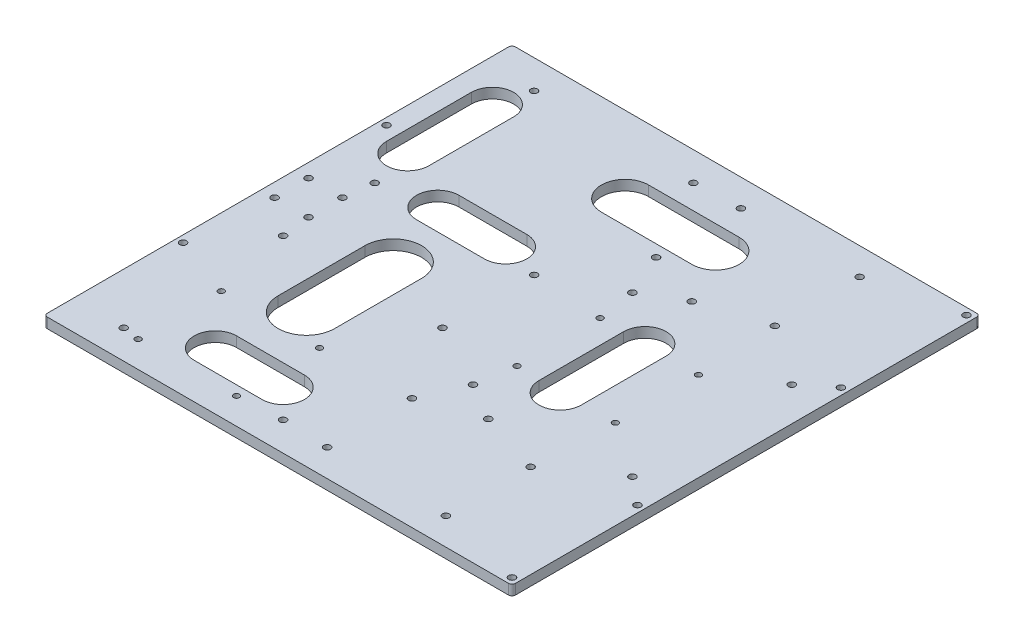
SolidWorks part; units mm, degrees
ref_plane "Спереди" through (0, 0, 0) normal (0, 0, 1) x (1, 0, 0)
ref_plane "Сверху" through (0, 0, 0) normal (0, 1, 0) x (1, 0, 0)
ref_plane "Справа" through (0, 0, 0) normal (1, 0, 0) x (0, 0, -1)
sketch "Эскиз1" plane through (0, 0, 0) normal (0, 1, 0) x (1, 0, 0)
  line L1 (-138, -138) -> (138, -138)
  line L2 (-138, -138) -> (-138, 138)
  line L3 (-138, 138) -> (138, 138)
  line L4 (138, -138) -> (138, 138)
  line L5 (0, 138) -> (0, -138) construction
  line L6 (-138, 0) -> (138, 0) construction
  point P0 (0, 0)
  dimension "D1" = 276
  dimension "D2" = 276
extrude "Бобышка-Вытянуть1" add sketch "Эскиз1" along normal blind 6
fillet "Скругление1" radius 2 4 edges at (138, 3, 138) (-138, 3, 138) (-138, 3, -138) (138, 3, -138)
sketch "Эскиз2" plane through (0, 6, 0) normal (0, 1, 0) x (1, 0, 0)
  line L0 (0, 147.7994) -> (0, 0) construction
  line L1 (0, 0) -> (-164.0684, 0) construction
  line L2 (-164.0684, 0) -> (215.1731, 0) construction
  circle A0 centre (-134, 60) radius 2
  circle A1 centre (134, 60) radius 2
  circle A2 centre (134, -60) radius 2
  circle A3 centre (-134, -60) radius 2
  circle A4 centre (46, 60) radius 2
  circle A5 centre (46, -60) radius 2
  circle A6 centre (134, 134) radius 2
  circle A7 centre (134, -134) radius 2
  dimension "D1" = 134
  dimension "D2" = 60
  dimension "D4" = 134
  dimension "D3" = 46
  dimension "D5" = 134
extrude "Вырез-Вытянуть1" cut sketch "Эскиз2" against normal blind 6
sketch "Эскиз10" plane through (0, 6, 0) normal (0, 1, 0) x (1, 0, 0)
  line L0 (0, 0) -> (99.2175, -171.8497) construction
  line L1 (0, 0) -> (206.3493, 0) construction
  line L2 (13, -97) -> (83, -97) construction
  line L3 (13, 72) -> (83, 72) construction
  line L4 (13, 72) -> (13, 122) construction
  line L5 (13, 122) -> (83, 122) construction
  line L6 (83, 72) -> (83, 122) construction
  line L7 (48, 122) -> (48, 72) construction
  line L8 (13, 97) -> (83, 97) construction
  line L9 (48, -122) -> (48, -72) construction
  line L15 (136, 138) -> (-136, 138) construction
  line L16 (-27.8464, 0) -> (-120, 0) construction
  line L17 (-120, 0) -> (0, 0) construction
  line L19 (-130, -10) -> (-110, -10) construction
  line L20 (-130, -10) -> (-130, 10) construction
  line L21 (-130, 10) -> (-110, 10) construction
  line L22 (-110, -10) -> (-110, 10) construction
  line L23 (-120, 10) -> (-120, -10) construction
  line L24 (-130, 0) -> (-110, 0) construction
  line L25 (0, 0) -> (99.2175, 171.8497) construction
  line L26 (83, -72) -> (83, -122) construction
  line L27 (13, -122) -> (83, -122) construction
  line L28 (13, -72) -> (13, -122) construction
  line L29 (13, -72) -> (83, -72) construction
  line L30 (138, -136) -> (138, 136) construction
  line L32 (138, -138) -> (60, -138) construction
  line L33 (138, -138) -> (138, -103.923) construction
  line L34 (138, -103.923) -> (60, -103.923) construction
  line L35 (60, -138) -> (60, -103.923) construction
  line L36 (83, 122) -> (60, 122) construction
  line L37 (83, 122) -> (83, 103.923) construction
  line L38 (83, 103.923) -> (60, 103.923) construction
  line L39 (60, 122) -> (60, 103.923) construction
  circle A0 centre (13, 122) radius 2
  circle A1 centre (83, 122) radius 2
  circle A2 centre (13, 72) radius 2
  circle A3 centre (83, 72) radius 2
  circle A8 centre (-130, 10) radius 2
  circle A9 centre (-110, 10) radius 2
  circle A10 centre (-110, -10) radius 2
  circle A11 centre (-130, -10) radius 2
  circle A13 centre (0, 0) radius 120 construction
  circle A14 centre (83, -72) radius 2
  circle A15 centre (13, -72) radius 2
  circle A16 centre (83, -122) radius 2
  circle A17 centre (13, -122) radius 2
  point P5 (48, 97)
  point P25 (48, -97)
  dimension "D3" = 4
  dimension "D9" = 23
  dimension "D10" = 18.077
  dimension "D13" = 72
  dimension "D14" = 13
  dimension "D15" = 110
  dimension "D1" = 50
  dimension "D2" = 70
  dimension "D4" = 90
  dimension "D5" = 16
  dimension "D6" = 20
  dimension "D7" = 20
  dimension "D8" = 120
  dimension "D11" = 78
  dimension "D12" = 34.077
extrude "Под стойки и сервы" cut sketch "Эскиз10" against normal blind 7
sketch "Эскиз3" plane through (0, 6, 0) normal (0, 1, 0) x (1, 0, 0)
  line L0 (0, 147.4317) -> (0, 0) construction
  line L1 (-193.8488, 0) -> (193.8488, 0) construction
  line L2 (138, -136) -> (138, 136) construction
  line L7 (43, 82) -> (43, -82) construction
  line L13 (43, 75) -> (43, -75) construction
  line L14 (-117, -82) -> (33, -82) construction
  line L16 (-117, 82) -> (33, 82) construction
  line L18 (-42, 82) -> (-42, -82) construction
  line L19 (-89.5005, 0) -> (60.4995, 0) construction
  line L20 (-124, -75) -> (40, -75) construction
  line L22 (-124, 75) -> (40, 75) construction
  line L24 (-42, 75) -> (-42, -75) construction
  line L25 (-96.5005, 0) -> (67.4995, 0) construction
  circle A0 centre (-32, 82) radius 2
  circle A1 centre (118, 82) radius 2
  circle A2 centre (125, 75) radius 2
  circle A3 centre (-39, 75) radius 2
  circle A4 centre (118, -82) radius 2
  circle A5 centre (125, -75) radius 2
  circle A6 centre (-32, -82) radius 2
  circle A7 centre (-39, -75) radius 2
  circle A8 centre (-124, 75) radius 2
  circle A10 centre (40, 75) radius 2
  circle A11 centre (33, 82) radius 2
  circle A12 centre (40, -75) radius 2
  circle A13 centre (33, -82) radius 2
  circle A14 centre (-117, -82) radius 2
  circle A15 centre (-124, -75) radius 2
  circle A16 centre (-117, 82) radius 2
  point P3 (43, 0)
  point P8 (43, 0)
  point P22 (-42, 0)
  point P24 (-42, 0)
  dimension "D3" = 95
  dimension "D1" = 150
  dimension "D2" = 164
  dimension "D4" = 150
  dimension "D5" = 164
  dimension "D6" = 180
extrude "150х164" [suppressed] cut sketch "Эскиз3" against normal blind 6
sketch "Эскиз7" plane through (0, 6, 0) normal (0, 1, 0) x (1, 0, 0)
  line L0 (-167.0096, 52) -> (194.2165, 52) construction
  line L2 (-18, 26) -> (98, 26) construction
  line L3 (-18, 26) -> (-18, 78) construction
  line L4 (-18, 78) -> (98, 78) construction
  line L5 (98, 26) -> (98, 78) construction
  line L6 (40, 78) -> (40, 26) construction
  line L7 (-18, 52) -> (98, 52) construction
  line L8 (136, 138) -> (-136, 138) construction
  circle A0 centre (-18, 78) radius 1.75
  circle A1 centre (-18, 26) radius 1.75
  circle A2 centre (98, 78) radius 1.75
  circle A3 centre (98, 26) radius 1.75
  point P2 (40, 52)
  dimension "D3" = 3.5
  dimension "D1" = 116
  dimension "D2" = 52
  dimension "D4" = 40
  dimension "D5" = 60
extrude "Jetson" [suppressed] cut sketch "Эскиз7" against normal blind 6
sketch "Эскиз9" plane through (0, 6, 0) normal (0, 1, 0) x (1, 0, 0)
  line L0 (-18.2911, 15.2367) -> (-18.2911, -61.2367) construction
  line L1 (-18.2911, -61.2367) -> (91.6393, -61.2367) construction
  line L2 (91.6393, -61.2367) -> (91.6393, -138) construction
  line L3 (-136, -138) -> (136, -138) construction
  line L4 (91.6393, -138) -> (129.5083, -138) construction
  line L5 (129.5083, -138) -> (129.5083, 138) construction
  line L6 (136, 138) -> (-136, 138) construction
  line L7 (129.5083, 138) -> (112.5959, 138) construction
  line L8 (112.5959, 138) -> (112.5959, 17.8103) construction
  line L9 (112.5959, 17.8103) -> (-18.2911, 17.8103) construction
  line L10 (-18.2911, 17.8103) -> (-18.2911, 15.2367) construction
  line L11 (-18.2911, -23) -> (230.269, -23) construction
  line L12 (138, -136) -> (138, 136) construction
  line L13 (-7, 2) -> (-7, -48) construction
  line L14 (43, 2) -> (43, -48) construction
  line L15 (43, -48) -> (83, -48) construction
  line L16 (83, -48) -> (83, 2) construction
  line L17 (83, 2) -> (123, 2) construction
  line L18 (123, 2) -> (123, -48) construction
  line L19 (98, -17) -> (128, -17) construction
  line L26 (98, -17) -> (98, 13) construction
  line L27 (98, 13) -> (128, 13) construction
  line L28 (128, -17) -> (128, 13) construction
  line L29 (113, 13) -> (113, -17) construction
  line L30 (98, -2) -> (128, -2) construction
  circle A0 centre (-7, 2) radius 1.8
  circle A1 centre (43, 2) radius 1.8
  circle A2 centre (83, 2) radius 1.8
  circle A3 centre (123, 2) radius 1.8
  circle A4 centre (123, -48) radius 1.8
  circle A5 centre (83, -48) radius 1.8
  circle A6 centre (43, -48) radius 1.8
  circle A7 centre (-7, -48) radius 1.8
  circle A8 centre (43, -23) radius 1.8
  circle A9 centre (-7, -23) radius 1.8
  circle A10 centre (83, -23) radius 1.8
  circle A11 centre (123, -23) radius 1.8
  circle A12 centre (123, 62) radius 1.8
  circle A13 centre (123, 122) radius 1.8
  circle A15 centre (123, -108) radius 1.8
  circle A20 centre (98, 13) radius 1.8
  circle A21 centre (128, 13) radius 1.8
  circle A22 centre (98, -17) radius 1.8
  circle A23 centre (128, -17) radius 1.8
  circle A24 centre (98, -29) radius 1.8
  circle A25 centre (128, -29) radius 1.8
  circle A26 centre (128, -59) radius 1.8
  circle A27 centre (98, -59) radius 1.8
  point P61 (113, -2)
  dimension "D1" = 3.6
  dimension "D2" = 50
  dimension "D3" = 40
  dimension "D4" = 40
  dimension "D12" = 30
  dimension "D5" = 25
  dimension "D6" = 60
  dimension "D7" = 60
  dimension "D8" = 115
  dimension "D9" = 15
  dimension "D13" = 30
  dimension "D14" = 10
  dimension "D15" = 140
extrude "Вырез-Вытянуть8" [suppressed] cut sketch "Эскиз9" against normal blind 6
sketch "Эскиз4" plane through (0, 6, 0) normal (0, 1, 0) x (1, 0, 0)
  line L0 (-244.2183, 0) -> (0, 0) construction
  line L1 (0, 0) -> (0, 146.3288) construction
  line L2 (-177.488, 74) -> (64.2486, 74) construction
  line L3 (-138, 136) -> (-138, -136) construction
  line L4 (-108, 27) -> (-14, 27) construction
  line L5 (-108, 27) -> (-108, 121) construction
  line L6 (-108, 121) -> (-14, 121) construction
  line L7 (-14, 27) -> (-14, 121) construction
  line L8 (-61, 121) -> (-61, 27) construction
  line L9 (-108, 74) -> (-14, 74) construction
  line L10 (0, 0) -> (256.1096, 0) construction
  line L11 (24, -47) -> (118, -47) construction
  line L12 (24, -47) -> (24, 47) construction
  line L13 (24, 47) -> (118, 47) construction
  line L14 (118, -47) -> (118, 47) construction
  line L15 (71, 47) -> (71, -47) construction
  line L16 (24, 0) -> (118, 0) construction
  line L17 (138, -136) -> (138, 136) construction
  circle A0 centre (-108, 121) radius 2
  circle A1 centre (-14, 121) radius 2
  circle A2 centre (-14, 27) radius 2
  circle A3 centre (-108, 27) radius 2
  circle A4 centre (-108, -27) radius 2
  circle A5 centre (-14, -27) radius 2
  circle A6 centre (-14, -121) radius 2
  circle A7 centre (-108, -121) radius 2
  circle A8 centre (24, 47) radius 2
  circle A9 centre (118, 47) radius 2
  circle A10 centre (118, -47) radius 2
  circle A11 centre (24, -47) radius 2
  point P6 (-61, 74)
  point P24 (71, 0)
  dimension "D5" = 94
  dimension "D9" = 47
  dimension "D1" = 94
  dimension "D2" = 94
  dimension "D3" = 74
  dimension "D4" = 30
  dimension "D6" = 94
  dimension "D7" = 20
  dimension "D8" = 118
extrude "94х94" cut sketch "Эскиз4" against normal blind 6
sketch "Эскиз8" plane through (0, 6, 0) normal (0, 1, 0) x (1, 0, 0)
  line L1 (27.4655, -24.5) -> (85.4655, -24.5) construction
  line L2 (27.4655, -24.5) -> (27.4655, 24.5) construction
  line L3 (27.4655, 24.5) -> (85.4655, 24.5) construction
  line L4 (85.4655, -24.5) -> (85.4655, 24.5) construction
  line L5 (56.4655, 24.5) -> (56.4655, -24.5) construction
  line L6 (27.4655, 0) -> (85.4655, 0) construction
  line L8 (0, 166.5491) -> (0, 0) construction
  line L9 (0, 0) -> (185.1673, 0) construction
  line L10 (-167.745, -98) -> (174.3629, -98) construction
  line L11 (-98, -122.5) -> (-40, -122.5) construction
  line L12 (-98, -122.5) -> (-98, -73.5) construction
  line L13 (-98, -73.5) -> (-40, -73.5) construction
  line L14 (-40, -122.5) -> (-40, -73.5) construction
  line L15 (-69, -73.5) -> (-69, -122.5) construction
  line L16 (-98, -98) -> (-40, -98) construction
  line L17 (-136, -138) -> (136, -138) construction
  line L18 (-138, 136) -> (-138, -136) construction
  circle A0 centre (85.4655, 24.5) radius 1.75
  circle A1 centre (27.4655, 24.5) radius 1.75
  circle A2 centre (27.4655, -24.5) radius 1.75
  circle A3 centre (85.4655, -24.5) radius 1.75
  circle A4 centre (-40, -73.5) radius 1.75
  circle A5 centre (-98, -73.5) radius 1.75
  circle A6 centre (-98, -122.5) radius 1.75
  circle A7 centre (-40, -122.5) radius 1.75
  point P0 (56.4655, 0)
  point P4 (-69, -98)
  dimension "D5" = 3.5
  dimension "D1" = 58
  dimension "D2" = 49
  dimension "D3" = 40
  dimension "D4" = 40
extrude "RPi4" cut sketch "Эскиз8" against normal blind 6
sketch "Эскиз6" plane through (0, 6, 0) normal (0, 1, 0) x (1, 0, 0)
  line L0 (-70.6279, -104.2964) -> (-30.6279, -104.2964) construction
  line L3 (0, 165.0655) -> (0, 0) construction
  line L4 (0, 0) -> (164.436, 0) construction
  line L5 (-70.6279, -91.7964) -> (-30.6279, -91.7964)
  line L9 (-76.8541, 33.0775) -> (-36.8541, 33.0775) construction
  line L10 (-76.8541, 45.5775) -> (-36.8541, 45.5775)
  line L11 (-76.8541, 20.5775) -> (-36.8541, 20.5775)
  line L13 (-70.6279, -116.7964) -> (-30.6279, -116.7964)
  line L16 (-62.1479, -7.8884) -> (-62.1479, -59.1081) construction
  line L20 (-113.2922, 101.779) -> (-113.2922, 51.779) construction
  line L21 (-125.7922, 101.779) -> (-125.7922, 51.779)
  line L22 (-100.7922, 101.779) -> (-100.7922, 51.779)
  line L23 (-26.2076, 92.8656) -> (27.1824, 92.8656) construction
  line L24 (-26.2076, 106.7739) -> (27.1824, 106.7739)
  line L25 (-26.2076, 78.9573) -> (27.1824, 78.9573)
  line L26 (-78.8638, -7.8884) -> (-78.8638, -59.1081)
  line L29 (-45.4321, -7.8884) -> (-45.4321, -59.1081)
  line L30 (53.8487, 24.5334) -> (53.8487, -25.4666) construction
  line L31 (41.3487, 24.5334) -> (41.3487, -25.4666)
  line L32 (66.3487, 24.5334) -> (66.3487, -25.4666)
  arc A4 (-76.8541, 45.5775) -> (-76.8541, 20.5775) centre (-76.8541, 33.0775) ccw
  arc A5 (-36.8541, 20.5775) -> (-36.8541, 45.5775) centre (-36.8541, 33.0775) ccw
  arc A10 (-125.7922, 101.779) -> (-100.7922, 101.779) centre (-113.2922, 101.779) cw
  arc A11 (-100.7922, 51.779) -> (-125.7922, 51.779) centre (-113.2922, 51.779) cw
  arc A12 (-26.2076, 106.7739) -> (-26.2076, 78.9573) centre (-26.2076, 92.8656) ccw
  arc A13 (27.1824, 78.9573) -> (27.1824, 106.7739) centre (27.1824, 92.8656) ccw
  arc A16 (-70.6279, -91.7964) -> (-70.6279, -116.7964) centre (-70.6279, -104.2964) ccw
  arc A17 (-30.6279, -116.7964) -> (-30.6279, -91.7964) centre (-30.6279, -104.2964) ccw
  arc A18 (-78.8638, -7.8884) -> (-45.4321, -7.8884) centre (-62.1479, -7.8884) cw
  arc A19 (-45.4321, -59.1081) -> (-78.8638, -59.1081) centre (-62.1479, -59.1081) cw
  arc A20 (41.3487, 24.5334) -> (66.3487, 24.5334) centre (53.8487, 24.5334) cw
  arc A21 (66.3487, -25.4666) -> (41.3487, -25.4666) centre (53.8487, -25.4666) cw
  point P2 (-50.6279, -104.2964)
  point P13 (-62.1479, -33.4983)
  point P22 (-56.8541, 33.0775)
  point P30 (53.8487, -0.4666)
  point P47 (-113.2922, 76.779)
  point P54 (0.4874, 92.8656)
extrude "Вырез-Вытянуть5" cut sketch "Эскиз6" against normal blind 6 contours A11 L22 A10 L21 | L25 A13 L24 A12 | L11 A5 L10 A4 | A19 L29 A18 L26 | A21 L32 A20 L31 | L13 A17 L5 A16 region at (-50.6279, 6, 104.2964) region at (-56.8541, 6, -33.0775) region at (-113.2922, 6, -76.779) region at (0.4874, 6, -92.8656) region at (-62.1479, 6, 33.4983) region at (53.8487, 6, 0.4666)
